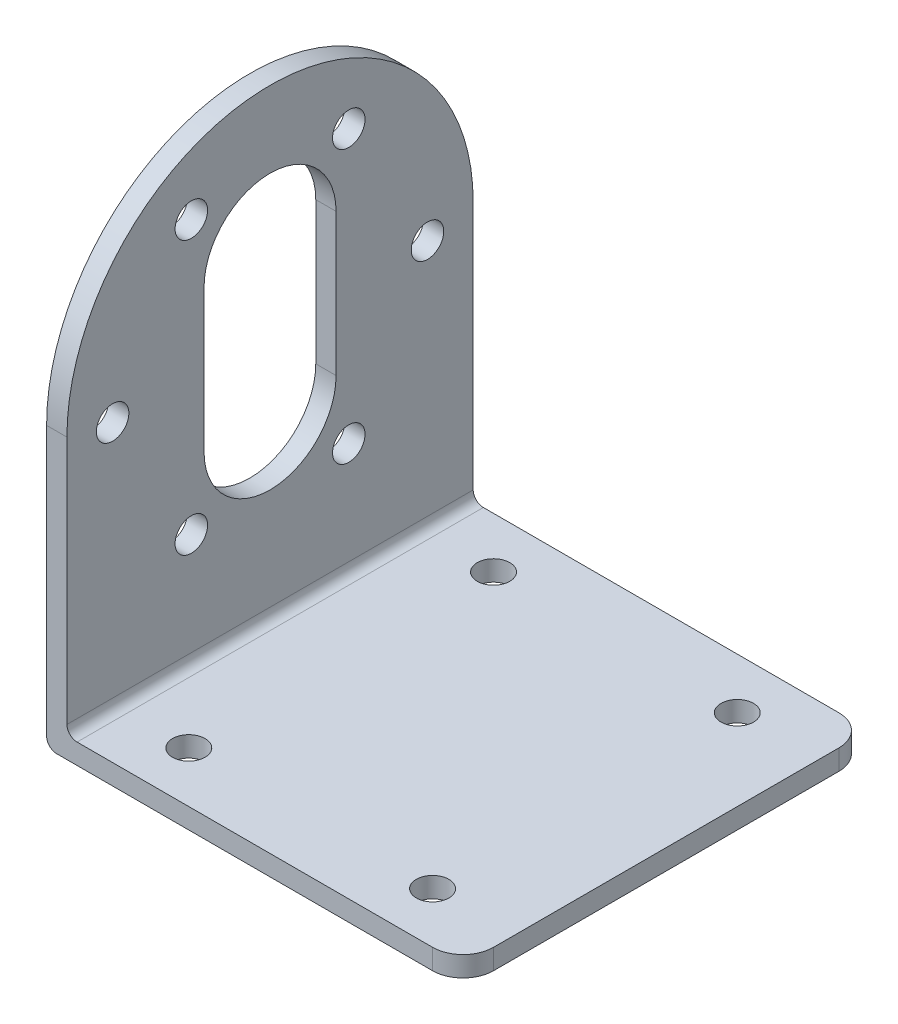
SolidWorks part; units mm, degrees
ref_plane "前视基准面" through (0, 0, 0) normal (0, 0, 1) x (1, 0, 0)
ref_plane "上视基准面" through (0, 0, 0) normal (0, 1, 0) x (1, 0, 0)
ref_plane "右视基准面" through (0, 0, 0) normal (1, 0, 0) x (0, 0, -1)
other "Configuration Table"
sketch "草图1" plane through (0, 0, 0) normal (0, 0, 1) x (1, 0, 0)
  line L0 (0, 0) -> (0, 47.5)
  line L1 (0, 47.5) -> (2, 47.5)
  line L2 (2, 47.5) -> (2, 2)
  line L3 (2, 2) -> (41, 2)
  line L4 (41, 2) -> (41, 0)
  line L5 (41, 0) -> (0, 0)
  dimension "D1" = 2
  dimension "D2" = 47.5
  dimension "D3" = 2
  dimension "D4" = 41
extrude "凸台-拉伸1" add sketch "草图1" along normal blind 40
fillet "圆角1" radius 1 2 edges at (0, 0, 20) (2, 2, 20)
sketch "草图3" plane through (0, 0, 0) normal (0, -1, 0) x (1, 0, 0)
  line L0 (1, 20) -> (41, 20) construction
  line L1 (1, 40) -> (1, 0) construction
  line L2 (41, 40) -> (41, 0) construction
  line L3 (33, 5) -> (33, 35) construction
  line L4 (9, 5) -> (9, 35) construction
  circle A4 centre (33, 35) radius 1.6
  circle A5 centre (33, 5) radius 1.6
  circle A6 centre (9, 35) radius 1.6
  circle A7 centre (9, 5) radius 1.6
  point P5 (9, 20)
  point P17 (33, 20)
  dimension "D3" = 3.2
  dimension "D4" = 3.2
  dimension "D7" = 3.2
  dimension "D8" = 3.2
  dimension "D1" = 30
  dimension "D2" = 8
  dimension "D5" = 30
  dimension "D6" = 24
extrude "切除-拉伸1" cut sketch "草图3" against normal blind 40
fillet "圆角2" radius 3 2 edges at (41, 1, 0) (41, 1, 40)
fillet "圆角3" 2 edges at (1, 47.5, 40) (1, 47.5, 0) type full round first side face at (10.4482, 12.8232, 40) second side face at (10.4482, 12.8232, 0) middle face at (1, 47.5, 20)
sketch "草图4" plane through (0, 0, 0) normal (-1, 0, 0) x (0, 0, 1)
  line L0 (20, 47.5) -> (20, 1) construction
  line L1 (0, 1) -> (40, 1) construction
  line L2 (40, 0) -> (0, 0) construction
  line L3 (20, 19.5) -> (20, 33.5) construction
  line L4 (13.5, 19.5) -> (13.5, 33.5)
  line L5 (26.5, 19.5) -> (26.5, 33.5)
  arc A0 (40, 27.5) -> (0, 27.5) centre (20, 27.5) ccw construction
  circle A1 centre (20, 26.5) radius 15.5
  circle A2 centre (35.5, 26.5) radius 1.6
  circle A3 centre (27.75, 13.0766) radius 1.6
  circle A4 centre (12.25, 13.0766) radius 1.6
  circle A5 centre (4.5, 26.5) radius 1.6
  circle A6 centre (12.25, 39.9234) radius 1.6
  circle A7 centre (27.75, 39.9234) radius 1.6
  arc A8 (13.5, 19.5) -> (26.5, 19.5) centre (20, 19.5) ccw
  arc A9 (26.5, 33.5) -> (13.5, 33.5) centre (20, 33.5) ccw
  point P7 (20, 26.5)
  point P26 (20, 26.5)
  point P27 (20, 26.5)
  dimension "D2" = 31
  dimension "D3" = 3.2
  dimension "D7" = 6.5
  dimension "D1" = 26.5
  dimension "D5" = 19.5
  dimension "D6" = 14
  dimension "D4" = 6
extrude "切除-拉伸2" cut sketch "草图4" against normal blind 40 contours L5 A9 L4 A8 | A1 A2 | A1 A2 | A7 | A6 | A5 | A4 | A3 region at (0, 26.5, 20) region at (0, 26.5, 34.8063) region at (0, 26.5, 36.164)
